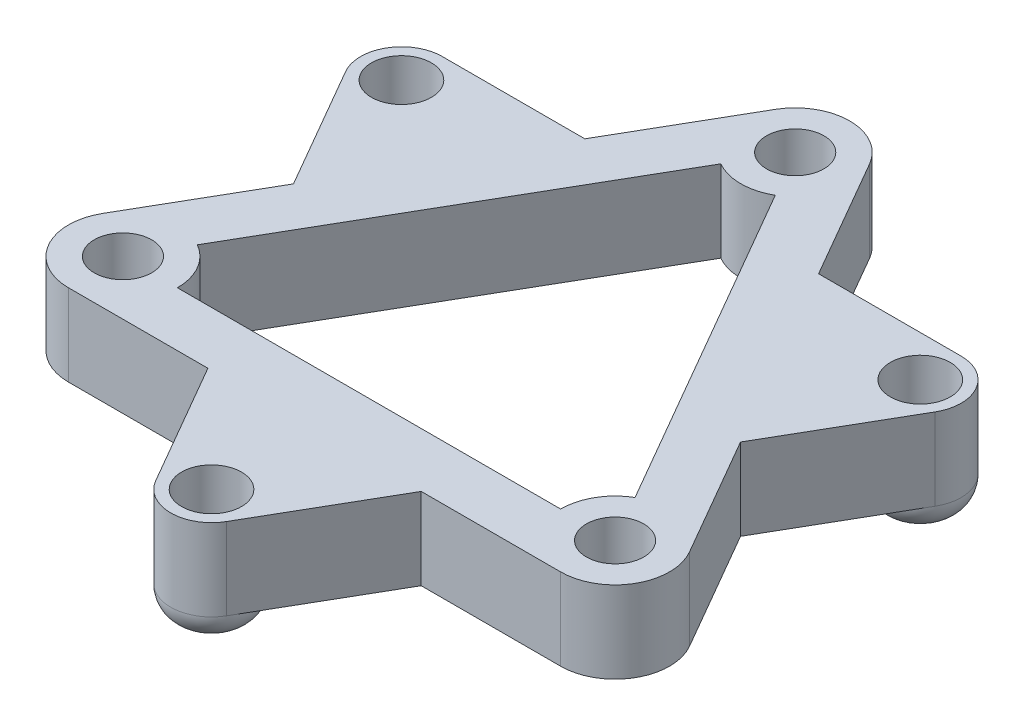
SolidWorks part; units mm, degrees
ref_plane "Front Plane" through (0, 0, 0) normal (0, 0, 1) x (1, 0, 0)
ref_plane "Top Plane" through (0, 0, 0) normal (0, 1, 0) x (1, 0, 0)
ref_plane "Right Plane" through (0, 0, 0) normal (1, 0, 0) x (0, 0, -1)
sketch "Sketch1" plane through (0, 0, 0) normal (0, 1, 0) x (1, 0, 0)
  line L0 (0, 0) -> (9.0359, 0)
  line L1 (10.7679, 3) -> (1.7321, 18.6506)
  line L2 (-1.7321, 18.6506) -> (-10.7679, 3)
  line L3 (-9.0359, 0) -> (0, 0)
  arc A0 (9.0359, 0) -> (10.7679, 3) centre (9.0359, 2) ccw
  arc A1 (-10.7679, 3) -> (-9.0359, 0) centre (-9.0359, 2) ccw
  arc A2 (1.7321, 18.6506) -> (-1.7321, 18.6506) centre (0, 17.6506) ccw
  circle A3 centre (0, 17.6506) radius 1.054
  circle A4 centre (-9.0359, 2) radius 1.054
  circle A5 centre (9.0359, 2) radius 1.054
  point P7 (12.5, 0)
  point P10 (-12.5, 0)
  point P13 (0, 21.6506)
  dimension "D5" = 2
  dimension "D1" = 60
  dimension "D2" = 60
  dimension "D3" = 25
  dimension "D4" = 12.5
extrude "Boss-Extrude1" add sketch "Sketch1" along normal blind 3
ref_point "Point1"
ref_axis "Axis1" through (0, 3, -7.2169) along (0, 1, 0)
sketch "Sketch3" plane through (0, 3, 0) normal (0, 1, 0) x (1, 0, 0)
  line L0 (-9.5263, 14.2169) -> (9.5263, 14.2169)
  line L1 (-1.299, -4.5331) -> (-10.8253, 11.9669)
  line L2 (1.299, -4.5331) -> (10.8253, 11.9669)
  arc A0 (-1.299, -4.5331) -> (1.299, -4.5331) centre (0, -3.7831) ccw
  circle A1 centre (0, -3.7831) radius 1.1
  arc A2 (-9.5263, 14.2169) -> (-10.8253, 11.9669) centre (-9.5263, 12.7169) ccw
  circle A3 centre (-9.5263, 12.7169) radius 1.1
  arc A4 (10.8253, 11.9669) -> (9.5263, 14.2169) centre (9.5263, 12.7169) ccw
  circle A5 centre (9.5263, 12.7169) radius 1.1
  point P14 (0, 7.2169)
  dimension "D1" = 11
  dimension "D2" = 3
extrude "Boss-Extrude2" add sketch "Sketch3" against normal up to surface (3 mm away) up to face at (-9.0359, 0, -0.946)
sketch "Sketch2" plane through (0, 3, 0) normal (0, 1, 0) x (1, 0, 0)
  line L0 (-1, 15.9186) -> (-8.0359, 3.7321)
  line L1 (-7.0359, 2) -> (7.0359, 2)
  line L2 (8.0359, 3.7321) -> (1, 15.9186)
  arc A0 (-1, 15.9186) -> (1, 15.9186) centre (0, 17.6506) ccw
  arc A1 (8.0359, 3.7321) -> (7.0359, 2) centre (9.0359, 2) ccw
  arc A2 (-7.0359, 2) -> (-8.0359, 3.7321) centre (-9.0359, 2) ccw
extrude "Cut-Extrude1" cut sketch "Sketch2" against normal through all
sketch "Sketch4" plane through (0, 0, 0) normal (0, -1, 0) x (1, 0, 0)
  circle A0 centre (0, 3.7831) radius 1.5
  circle A1 centre (9.5263, -12.7169) radius 1.5
  circle A2 centre (-9.5263, -12.7169) radius 1.5
extrude "Boss-Extrude3" add sketch "Sketch4" along normal blind 1
fillet "Fillet1" radius 1 3 edges at (-9.5263, -1, -14.2169) (9.5263, -1, -14.2169) (0, -1, 2.2831)
